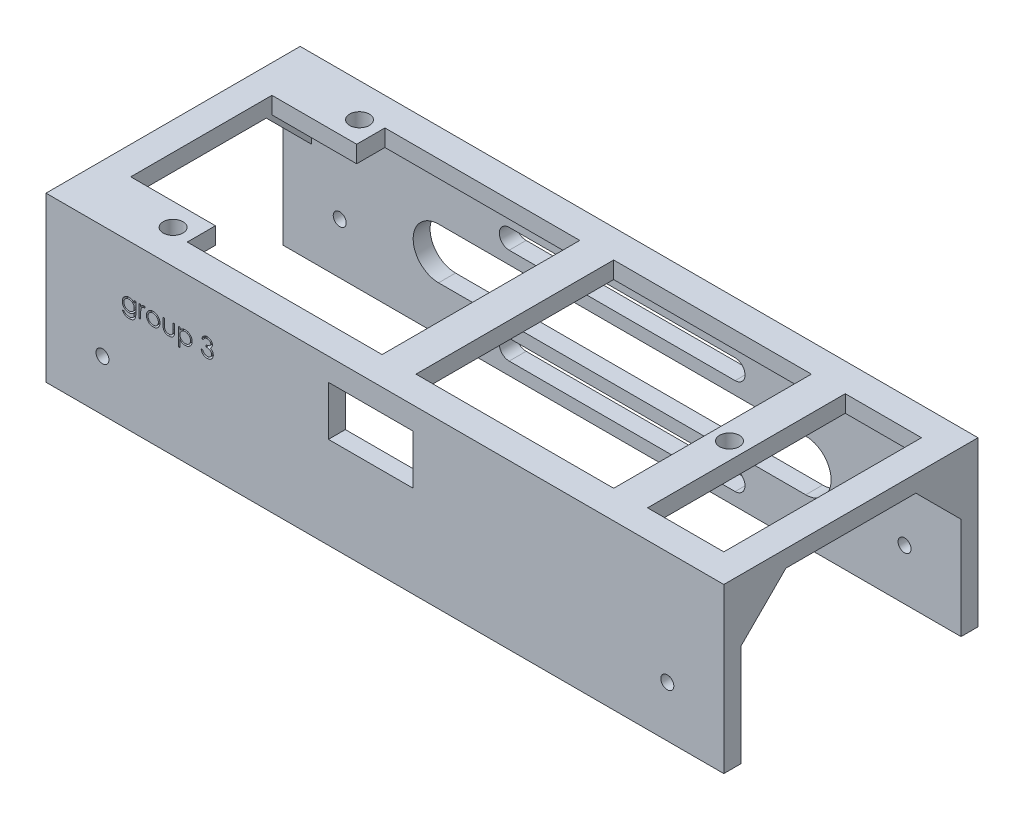
SolidWorks part; units mm, degrees
other "Markup1"
sketch "Sketch23" plane through (120, 29, 45) normal (0.0467, 0.9512, 0.3049) x (0.9885, 0, -0.1514)
sketch "Sketch24" plane through (120, 29, 45) normal (0.0467, 0.9512, 0.3049) x (0.9885, 0, -0.1514)
sketch "Sketch25" plane through (120, 29, 45) normal (0.0467, 0.9512, 0.3049) x (0.9885, 0, -0.1514)
sketch "Sketch26" plane through (120, 29, 45) normal (0.0467, 0.9512, 0.3049) x (0.9885, 0, -0.1514)
sketch "Sketch27" plane through (120, 29, 45) normal (0.0467, 0.9512, 0.3049) x (0.9885, 0, -0.1514)
ref_plane "Front Plane" through (0, 0, 0) normal (0, 0, 1) x (1, 0, 0)
ref_plane "Top Plane" through (0, 0, 0) normal (0, 1, 0) x (1, 0, 0)
ref_plane "Right Plane" through (0, 0, 0) normal (1, 0, 0) x (0, 0, -1)
sketch "Sketch1" plane through (0, 0, 0) normal (0, 0, 1) x (1, 0, 0)
  line L9 (21.172, -17.9478) -> (91.172, -17.9478)
  line L10 (21.172, -17.9478) -> (21.172, -40.3878)
  line L11 (4, -8) -> (200.227, -8) construction
  line L12 (4, -8) -> (-67.5185, -8) construction
  line L13 (21.172, -40.3878) -> (91.172, -40.3878)
  line L14 (91.172, -17.9478) -> (91.172, -40.3878)
  line L15 (0, 0) -> (120, 0)
  line L16 (0, 0) -> (0, 29)
  line L17 (0, 29) -> (120, 29)
  line L18 (120, 0) -> (120, 29)
  circle A0 centre (4, 7) radius 1.15
  circle A1 centre (4, 7) radius 15 construction
  circle A3 centre (77.172, -29.1678) radius 3.6067
  circle A4 centre (116, 7) radius 15 construction
  circle A5 centre (116, 7) radius 1.15
  point P19 (21.172, -29.1678)
  dimension "D4" = 30
  dimension "D2" = 14
  dimension "D7" = 30
  dimension "D11" = 4
  dimension "D13" = 2.3
  dimension "D14" = 2.3
  dimension "D3" = 70
  dimension "D5" = 22.44
  dimension "D6" = 120
  dimension "D8" = 29
  dimension "D9" = 4
  dimension "D10" = 7
  dimension "D12" = 7
extrude "Boss-Extrude5" add sketch "Sketch1" along normal blind 45 contours L16 L15 L18 L17
shell "Shell9" thickness 3 removed face at (120, 14.5, 22.5) removed face at (60, 0, 22.5) removed face at (0, 14.5, 22.5)
sketch "Sketch3" plane through (0, 0, 0) normal (0, 0, -1) x (-1, 0, 0)
  line L0 (0, 0) -> (-120, 0) construction
  line L1 (-120, 0) -> (-120, 29) construction
  line L2 (0, 0) -> (0, 29) construction
  circle A0 centre (-10, 9) radius 1.15
  circle A1 centre (-110, 9) radius 1.15
  dimension "D1" = 2.3
  dimension "D2" = 2.3
  dimension "D3" = 9
  dimension "D4" = 10
  dimension "D5" = 9
  dimension "D6" = 10
extrude "Cut-Extrude2" cut sketch "Sketch3" against normal blind 79
sketch "Sketch6" plane through (0, 0, 0) normal (0, 0, -1) x (-1, 0, 0)
  line L0 (-80, 21) -> (-40, 21) construction
  line L1 (-80, 22.75) -> (-40, 22.75)
  line L2 (-80, 19.25) -> (-40, 19.25)
  line L7 (-60, 29) -> (-60, 0) construction
  line L8 (-92.5, 12.5) -> (-27.5, 12.5) construction
  line L9 (-92.5, 17) -> (-27.5, 17)
  line L10 (-92.5, 8) -> (-27.5, 8)
  line L11 (-27.5, 12.5) -> (-14.9525, 12.5) construction
  line L12 (-80, 4) -> (-40, 4) construction
  line L13 (-80, 2.25) -> (-40, 2.25)
  line L14 (-80, 5.75) -> (-40, 5.75)
  line L15 (0, 0) -> (-120, 0) construction
  line L26 (0, 29) -> (-120, 29) construction
  arc A4 (-92.5, 17) -> (-92.5, 8) centre (-92.5, 12.5) ccw
  arc A5 (-80, 22.75) -> (-80, 19.25) centre (-80, 21) ccw
  arc A6 (-40, 19.25) -> (-40, 22.75) centre (-40, 21) ccw
  arc A7 (-27.5, 8) -> (-27.5, 17) centre (-27.5, 12.5) ccw
  arc A8 (-80, 2.25) -> (-80, 5.75) centre (-80, 4) cw
  arc A9 (-40, 5.75) -> (-40, 2.25) centre (-40, 4) cw
  point P5 (0, 0)
  point P6 (-57.3735, 12.5)
  point P8 (0, 0)
  point P9 (0, 0)
  point P10 (0, 0)
  point P11 (-60, 21)
  point P17 (0, 0)
  point P18 (0, 0)
  point P19 (-60, 12.5)
  point P21 (0, 0)
  point P31 (-60, 4)
  dimension "D3" = 20
  dimension "D8" = 1.75
  dimension "D13" = 4.5
  dimension "D2" = 8.5
  dimension "D16" = 65
  dimension "D19" = 16.5
extrude "Cut-Extrude8" cut sketch "Sketch6" against normal blind 23 contours L10 A7 L9 | L2 A6 L1 A5 | L13 A9 L14 A8 region at (60, 21, 0) region at (60, 12.5, 0)
sketch "Sketch7" plane through (0, 0, 45) normal (0, 0, 1) x (1, 0, 0)
  line L1 (50, 25) -> (65, 25)
  line L2 (50, 25) -> (50, 16.25)
  line L3 (50, 16.25) -> (65, 16.25)
  line L4 (65, 25) -> (65, 16.25)
  line L5 (0, 0) -> (120, 0) construction
  line L7 (0, 0) -> (0, 29) construction
  dimension "D1" = 50
  dimension "D2" = 15
  dimension "D3" = 8.75
  dimension "D4" = 25
extrude "Cut-Extrude9" cut sketch "Sketch7" against normal blind 20
sketch "Sketch13" plane through (0, 29, 0) normal (0, 1, 0) x (1, 0, 0)
  line L1 (0, 0) -> (120, 0) construction
  line L4 (5, -5) -> (115, -5)
  line L5 (5, -5) -> (5, -40)
  line L6 (5, -40) -> (115, -40)
  line L8 (0, -45) -> (0, 0) construction
  line L16 (115, -5) -> (115, -40)
  line L17 (120, -45) -> (120, 0) construction
  dimension "D1" = 5
  dimension "D2" = 5
  dimension "D5" = 5
  dimension "D6" = 35
extrude "Cut-Extrude14" cut sketch "Sketch13" against normal blind 10
sketch "Sketch17" plane through (0, 29, 0) normal (0, 1, 0) x (1, 0, 0)
  line L0 (0, -22.5) -> (120, -22.5) construction
  line L1 (5, -5) -> (20, -5)
  line L2 (5, -5) -> (5, -10)
  line L3 (5, -10) -> (20, -10)
  line L4 (20, -5) -> (20, -10)
  line L5 (5, -40) -> (20, -40)
  line L6 (5, -40) -> (5, -35)
  line L7 (5, -35) -> (20, -35)
  line L8 (20, -40) -> (20, -35)
  line L17 (0, -45) -> (0, 0) construction
  line L18 (120, -45) -> (120, 0) construction
  line L25 (115, -5) -> (5, -5) construction
  line L26 (95.5, -5) -> (101.5, -5)
  line L27 (95.5, -5) -> (95.5, -40)
  line L28 (95.5, -40) -> (101.5, -40)
  line L29 (101.5, -5) -> (101.5, -40)
  line L30 (5, -40) -> (115, -40) construction
  line L32 (54.5, -5) -> (60.5, -5)
  line L33 (54.5, -5) -> (54.5, -40)
  line L34 (54.5, -40) -> (60.5, -40)
  line L35 (60.5, -5) -> (60.5, -40)
  circle A0 centre (16.5, -39) radius 1.75
  circle A1 centre (16.5, -6) radius 1.75
  circle A2 centre (98.5, -22.5) radius 1.75
  point P41 (98.5, -5)
  line M10 (5, -40) -> (5, -5)
  line M11 (5, -5) -> (115, -5)
  line M13 (115, -40) -> (5, -40)
  dimension "D3" = 3.5
  dimension "D6" = 3.5
  dimension "D11" = 33
  dimension "D12" = 16.5
  dimension "D13" = 3.5
  dimension "D1" = 5
  dimension "D2" = 15
  dimension "D4" = 5
  dimension "D5" = 15
  dimension "D7" = 6
  dimension "D8" = 18.5
  dimension "D9" = 6
  dimension "D10" = 35
extrude "Boss-Extrude6" add sketch "Sketch17" against normal blind 3 contours A1 L3 L4 M11 M10 | L1 A1 | A0 L8 L7 M13 M10 | L5 A0 | L33 L32 L35 L34 | L27 L26 L29 L28 region at (12.0151, 29, 7.6523) region at (16.5, 29, 6.2435) region at (12.0151, 29, 37.3477) region at (16.5, 29, 38.7565)
extrude "Cut-Extrude16" cut sketch "Sketch17<4>" against normal blind 10 contours A2 L0 | L0 A2 | L1 A1 | L1 A1 | L5 A0 | L5 A0 | A2 region at (98.5, 29, 21.7573) region at (98.5, 29, 23.2427) region at (16.5, 29, 4.6937) region at (16.5, 29, 6.2435) region at (16.5, 29, 38.7565) region at (16.5, 29, 40.3063)
sketch "Sketch17<4>" plane through (0, 29, 0) normal (0, 1, 0) x (1, 0, 0) same geometry as "Sketch17"
sketch "Sketch20" plane through (0, 0, 45) normal (0, 0, 1) x (1, 0, 0)
  line L0 (13.2558, 18.0126) -> (38.9246, 18.0126) construction
  text T0 "group 3"
extrude "Cut-Extrude15" cut sketch "Sketch20" against normal blind 1.5
sketch "Sketch21" plane through (0, 0, 0) normal (-1, 0, 0) x (0, 0, 1)
  line L0 (3, 26) -> (3, 18)
  line L1 (3, 0) -> (3, 26) construction
  line L2 (3, 18) -> (11, 26)
  line L3 (42, 26) -> (3, 26) construction
  line L4 (11, 26) -> (3, 26)
  line L5 (42, 26) -> (34, 26)
  line L6 (34, 26) -> (42, 18)
  line L7 (42, 0) -> (42, 26) construction
  line L8 (42, 18) -> (42, 26)
  dimension "D1" = 8
  dimension "D2" = 8
  dimension "D3" = 8
  dimension "D4" = 8
extrude "Boss-Extrude7" add sketch "Sketch21" against normal blind 5
sketch "Sketch22" plane through (120, 0, 0) normal (1, 0, 0) x (0, 0, -1)
  line L0 (-42, 26) -> (-42, 18)
  line L1 (-42, 18) -> (-34, 26)
  line L2 (-34, 26) -> (-42, 26)
  line L3 (-11, 26) -> (-3, 26)
  line L4 (-3, 26) -> (-3, 18)
  line L5 (-3, 18) -> (-11, 26)
extrude "Boss-Extrude8" add sketch "Sketch22" against normal blind 5
equation "\"slot­_width\"=25.09"
